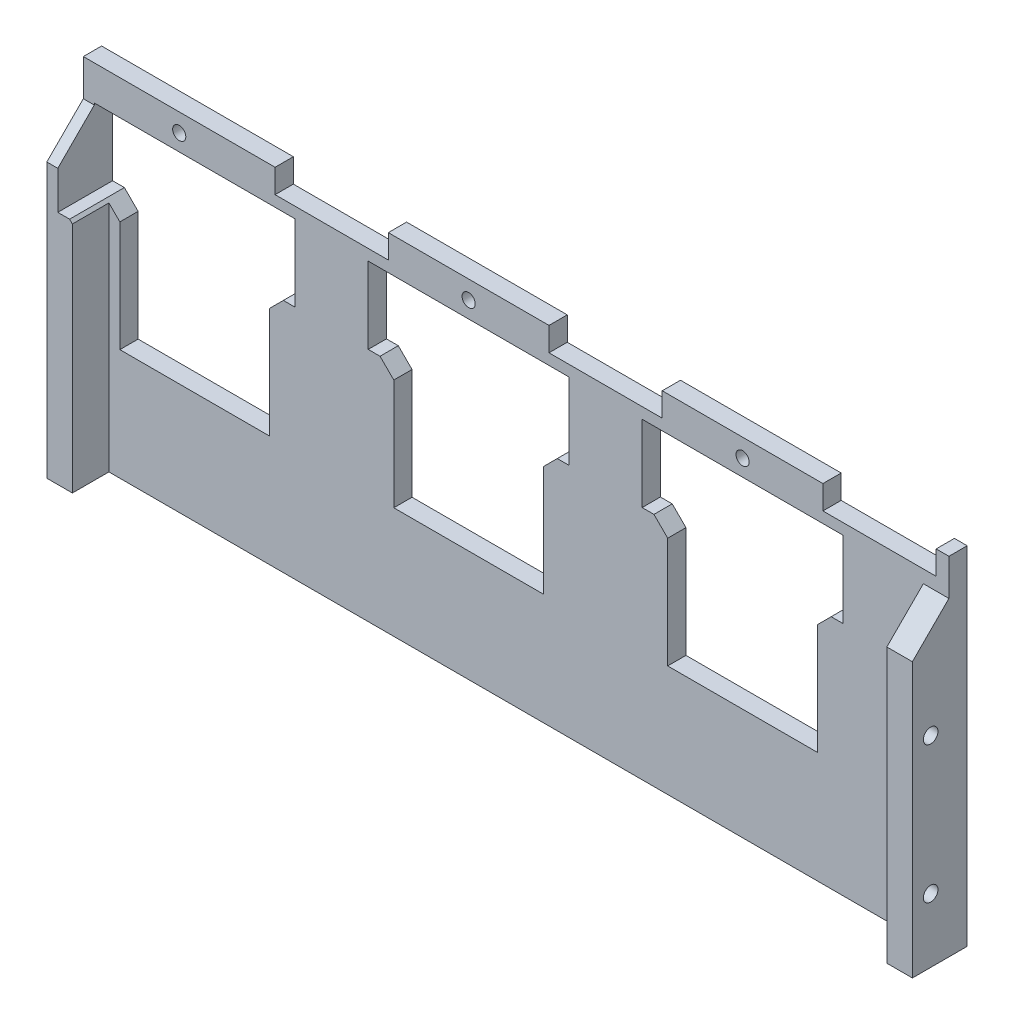
SolidWorks part; units mm, degrees
ref_plane "Płaszczyzna przednia" through (0, 0, 0) normal (0, 0, 1) x (1, 0, 0)
ref_plane "Płaszczyzna górna" through (0, 0, 0) normal (0, 1, 0) x (1, 0, 0)
ref_plane "Płaszczyzna prawa" through (0, 0, 0) normal (1, 0, 0) x (0, 0, -1)
sketch "Szkic1" plane through (0, 0, 0) normal (0, 0, 1) x (1, 0, 0)
  line L1 (-118.5, -72.5) -> (118.5, -72.5)
  line L2 (-118.5, -72.5) -> (-118.5, 72.5)
  line L3 (-118.5, 72.5) -> (118.5, 72.5)
  line L4 (118.5, -72.5) -> (118.5, 72.5)
  line L5 (0, 72.5) -> (0, -72.5) construction
  line L6 (-118.5, 0) -> (118.5, 0) construction
  point P0 (0, 0)
  dimension "D1" = 237
  dimension "D2" = 145
extrude "Dodanie-wyciągnięcie1" add sketch "Szkic1" along normal blind 5
sketch "Szkic2" plane through (0, 0, 5) normal (0, 0, 1) x (1, 0, 0)
  line L0 (118.5, -72.5) -> (118.5, 72.5) construction
  line L1 (118.5, 62.5) -> (111.5, 62.5)
  line L2 (118.5, 62.5) -> (118.5, -72.5)
  line L3 (118.5, -72.5) -> (111.5, -72.5)
  line L4 (111.5, 62.5) -> (111.5, -72.5)
  line L5 (115, -72.5) -> (115, 62.5) construction
  line L6 (118.5, -5) -> (111.5, -5) construction
  line L7 (118.5, 72.5) -> (-118.5, 72.5) construction
  line L9 (0, 0) -> (0, 72.5) construction
  line L10 (-118.5, -5) -> (-111.5, -5) construction
  line L11 (-115, -72.5) -> (-115, 62.5) construction
  line L12 (-111.5, 62.5) -> (-111.5, -72.5)
  line L13 (-118.5, -72.5) -> (-111.5, -72.5)
  line L14 (-118.5, 62.5) -> (-118.5, -72.5)
  line L15 (-118.5, 62.5) -> (-111.5, 62.5)
  line L16 (-118.5, -72.5) -> (118.5, -72.5) construction
  point P20 (-115, -5)
  point P300 (115, -5)
  dimension "D1" = 10
  dimension "D3" = 7
extrude "Dodanie-wyciągnięcie2" add sketch "Szkic2" along normal blind 10
sketch "Szkic3" plane through (118.5, 0, 0) normal (1, 0, 0) x (0, 0, -1)
  line L0 (-10, 62.5) -> (-10, -72.5) construction
  line L1 (-15, 62.5) -> (-5, 62.5) construction
  line L3 (0, -5) -> (-15, -5) construction
  line L5 (-15, -72.5) -> (-15, 62.5) construction
  line L6 (-15, -72.5) -> (-15, 62.5) construction
  line L7 (0, -72.5) -> (0, 72.5) construction
  line L8 (-15, -72.5) -> (0, -72.5) construction
  point P6 (-10, 32.5)
  point P7 (-10, -5)
  point P8 (-10, -42.5)
  dimension "D1" = 37.5
hole_wizard "Otwór Ø4.0 (4)1" positions "Szkic3" profile "Szkic4" hole size "Ø4.0" standard "DIN"
sketch "Szkic4" plane through (118.5, -42.5, 10) normal (0, 1, 0) x (0, 0, -1)
  line L0 (0, 0) -> (0, 6.7)
  line L1 (0, 6.7) -> (2, 6.7)
  line L2 (2, 6.7) -> (2, 0)
  line L5 (2, 0) -> (0, 0)
  line L10 (0, 6.7) -> (-2, 6.7) construction
  line L11 (0, -6.35) -> (0, 107.95) construction
  dimension "Średnica otworu" = 4
  dimension "Głębokość otworu" = 6.7
  dimension "Kąt wiertła" = 180
ref_plane "Płaszczyzna1" through (0, 0, 0) normal (-1, 0, 0) x (0, 0, 1)
mirror "Lustro1" about plane through (0, 0, 0) normal (-1, 0, 0) of "Otwór Ø4.0 (4)1"
chamfer "Sfazowanie1" distance 10 angle 45 2 edges at (-115, 62.5, 15) (115, 62.5, 15)
sketch "Szkic5" plane through (0, 0, 0) normal (0, 0, -1) x (-1, 0, 0)
  line L1 (-86, 42.5546) -> (-86, 42.5)
  line L2 (-84.5, 72.5) -> (-114.5, 72.5)
  line L4 (-11, 42.5546) -> (-11, 42.5)
  line L6 (-9.5, 72.5) -> (-39.5, 72.5)
  line L7 (64, 42.5546) -> (64, 42.5)
  line L12 (-86.2617, 42.0546) -> (-86.2617, 42.0546)
  line L15 (-86.2617, 42.0546) -> (-85.3536, 41.1464)
  line L16 (-85.3536, 41.1464) -> (-82.5, 38.2929)
  line L17 (-82.5, 38.2929) -> (-82.5, 8)
  line L22 (-82.5, 8) -> (-41.5, 8)
  line L39 (-41.5, 8) -> (-41.5, 38.2929)
  line L43 (111, 41.5) -> (112, 42.5) construction
  line L44 (-41.5, 38.2929) -> (-38.6464, 41.1464)
  line L46 (112, 42.5) -> (112, 48.5) construction
  line L48 (-38.6464, 41.1464) -> (-37.7383, 42.0546)
  line L49 (108, 38.5) -> (111, 41.5) construction
  line L57 (-37.7383, 42.0546) -> (-37.7383, 42.0546)
  line L58 (61, 62.5) -> (61, 42.5546) construction
  line L59 (61, 42.5546) -> (67.7879, 42.5546) construction
  line L86 (-37.7383, 42.0546) -> (-34.5, 42.0546)
  line L88 (-34.5, 42.0546) -> (-34.5, 63)
  line L90 (-34.5, 63) -> (-89.5, 63)
  line L94 (-89.5, 63) -> (-89.5, 42.0546)
  line L102 (-89.5, 42.0546) -> (-86.2617, 42.0546)
  line L103 (-84, 73) -> (-115, 73)
  line L104 (108.2121, 42.5546) -> (115, 42.5546) construction
  line L105 (115, 42.5546) -> (115, 62.5) construction
  line L106 (115, 62.5) -> (61, 62.5) construction
  line L109 (64, 42.5) -> (65, 41.5) construction
  line L110 (-115, 73) -> (-115, 66)
  line L115 (-115, 66) -> (-84, 66)
  line L121 (-84, 66) -> (-84, 73)
  line L122 (65, 41.5) -> (68, 38.5) construction
  line L123 (-11.2617, 42.0546) -> (-11.2617, 42.0546)
  line L127 (-11.2617, 42.0546) -> (-10.3536, 41.1464)
  line L128 (-10.3536, 41.1464) -> (-7.5, 38.2929)
  line L129 (-7.5, 38.2929) -> (-7.5, 8)
  line L132 (-7.5, 8) -> (33.5, 8)
  line L134 (33.5, 8) -> (33.5, 38.2929)
  line L135 (33.5, 38.2929) -> (36.3536, 41.1464)
  line L168 (36.3536, 41.1464) -> (37.2617, 42.0546)
  line L175 (37.2617, 42.0546) -> (37.2617, 42.0546)
  line L183 (37.2617, 42.0546) -> (40.5, 42.0546)
  line L200 (40.5, 42.0546) -> (40.5, 63)
  line L201 (40.5, 63) -> (-14.5, 63)
  line L206 (-14.5, 63) -> (-14.5, 42.0546)
  line L207 (-14.5, 42.0546) -> (-11.2617, 42.0546)
  line L208 (-9, 73) -> (-40, 73)
  line L209 (-40, 73) -> (-40, 66)
  line L210 (-40, 66) -> (-9, 66)
  line L212 (68, 38.5) -> (68, 8.5) construction
  line L213 (68, 8.5) -> (108, 8.5) construction
  line L214 (108, 8.5) -> (108, 38.5) construction
  line L215 (-9, 66) -> (-9, 73)
  line L216 (36, 41.5) -> (37, 42.5) construction
  line L225 (37, 42.5) -> (37, 48.5) construction
  line L230 (63.7383, 42.0546) -> (63.7383, 42.0546)
  line L277 (33, 38.5) -> (36, 41.5) construction
  line L278 (63.7383, 42.0546) -> (64.6464, 41.1464)
  line L279 (-14, 62.5) -> (-14, 42.5546) construction
  line L280 (-14, 42.5546) -> (-7.2121, 42.5546) construction
  line L288 (64.6464, 41.1464) -> (67.5, 38.2929)
  line L289 (67.5, 38.2929) -> (67.5, 8)
  line L290 (67.5, 8) -> (108.5, 8)
  line L292 (108.5, 8) -> (108.5, 38.2929)
  line L293 (108.5, 38.2929) -> (111.3536, 41.1464)
  line L294 (111.3536, 41.1464) -> (112.2617, 42.0546)
  line L296 (33.2121, 42.5546) -> (40, 42.5546) construction
  line L309 (40, 42.5546) -> (40, 62.5) construction
  line L310 (40, 62.5) -> (-14, 62.5) construction
  line L311 (-11, 42.5) -> (-10, 41.5) construction
  line L312 (112.2617, 42.0546) -> (112.2617, 42.0546)
  line L314 (112.2617, 42.0546) -> (115.5, 42.0546)
  line L318 (115.5, 42.0546) -> (115.5, 63)
  line L320 (-10, 41.5) -> (-7, 38.5) construction
  line L333 (115.5, 63) -> (60.5, 63)
  line L334 (60.5, 63) -> (60.5, 42.0546)
  line L335 (60.5, 42.0546) -> (63.7383, 42.0546)
  line L336 (35, 73) -> (35, 66)
  line L337 (35, 66) -> (66, 66)
  line L338 (66, 66) -> (66, 73)
  line L340 (66, 73) -> (35, 73)
  line L349 (-7, 38.5) -> (-7, 8.5) construction
  line L350 (-7, 8.5) -> (33, 8.5) construction
  line L351 (33, 8.5) -> (33, 38.5) construction
  line L352 (-42, 38.5) -> (-39, 41.5) construction
  line L355 (-39, 41.5) -> (-38, 42.5) construction
  line L356 (-38, 42.5) -> (-38, 48.5) construction
  line L358 (-86, 42.5) -> (-85, 41.5) construction
  line L362 (-85, 41.5) -> (-82, 38.5) construction
  line L364 (-89, 62.5) -> (-89, 42.5546) construction
  line L365 (-89, 42.5546) -> (-82.2121, 42.5546) construction
  line L373 (-41.7879, 42.5546) -> (-35, 42.5546) construction
  line L374 (-35, 42.5546) -> (-35, 62.5) construction
  line L375 (-35, 62.5) -> (-89, 62.5) construction
  line L391 (-82, 38.5) -> (-82, 8.5) construction
  line L392 (-82, 8.5) -> (-42, 8.5) construction
  line L393 (-42, 8.5) -> (-42, 38.5) construction
  line L395 (35.5, 90.5) -> (35.5, 66.5) construction
  line L396 (35.5, 66.5) -> (65.5, 66.5) construction
  line L397 (65.5, 66.5) -> (65.5, 90.5) construction
  line L399 (-39.5, 90.5) -> (-39.5, 66.5) construction
  line L400 (-39.5, 66.5) -> (-9.5, 66.5) construction
  line L401 (-9.5, 66.5) -> (-9.5, 90.5) construction
  line L402 (-114.5, 90.5) -> (-114.5, 66.5) construction
  line L403 (-114.5, 66.5) -> (-84.5, 66.5) construction
  line L404 (-84.5, 66.5) -> (-84.5, 90.5) construction
  line L407 (111, 41.5) -> (112, 42.5)
  line L408 (112, 42.5) -> (112, 42.5546)
  line L410 (108, 38.5) -> (111, 41.5)
  line L412 (61, 62.5) -> (61, 42.5546)
  line L413 (61, 42.5546) -> (64, 42.5546)
  line L421 (112, 42.5546) -> (115, 42.5546)
  line L422 (115, 42.5546) -> (115, 62.5)
  line L423 (115, 62.5) -> (61, 62.5)
  line L424 (64, 42.5) -> (65, 41.5)
  line L428 (65, 41.5) -> (68, 38.5)
  line L445 (68, 38.5) -> (68, 8.5)
  line L446 (68, 8.5) -> (108, 8.5)
  line L447 (108, 8.5) -> (108, 38.5)
  line L449 (36, 41.5) -> (37, 42.5)
  line L450 (37, 42.5) -> (37, 42.5546)
  line L452 (33, 38.5) -> (36, 41.5)
  line L454 (-14, 62.5) -> (-14, 42.5546)
  line L455 (-14, 42.5546) -> (-11, 42.5546)
  line L463 (37, 42.5546) -> (40, 42.5546)
  line L464 (40, 42.5546) -> (40, 62.5)
  line L465 (40, 62.5) -> (-14, 62.5)
  line L466 (-11, 42.5) -> (-10, 41.5)
  line L470 (-10, 41.5) -> (-7, 38.5)
  line L487 (-7, 38.5) -> (-7, 8.5)
  line L488 (-7, 8.5) -> (33, 8.5)
  line L489 (33, 8.5) -> (33, 38.5)
  line L490 (-42, 38.5) -> (-39, 41.5)
  line L493 (-39, 41.5) -> (-38, 42.5)
  line L494 (-38, 42.5) -> (-38, 42.5546)
  line L496 (-86, 42.5) -> (-85, 41.5)
  line L500 (-85, 41.5) -> (-82, 38.5)
  line L502 (-89, 62.5) -> (-89, 42.5546)
  line L503 (-89, 42.5546) -> (-86, 42.5546)
  line L511 (-38, 42.5546) -> (-35, 42.5546)
  line L512 (-35, 42.5546) -> (-35, 62.5)
  line L513 (-35, 62.5) -> (-89, 62.5)
  line L529 (-82, 38.5) -> (-82, 8.5)
  line L530 (-82, 8.5) -> (-42, 8.5)
  line L531 (-42, 8.5) -> (-42, 38.5)
  line L533 (35.5, 72.5) -> (35.5, 66.5)
  line L534 (35.5, 66.5) -> (65.5, 66.5)
  line L535 (65.5, 66.5) -> (65.5, 72.5)
  line L537 (-39.5, 72.5) -> (-39.5, 66.5)
  line L538 (-39.5, 66.5) -> (-9.5, 66.5)
  line L539 (-9.5, 66.5) -> (-9.5, 72.5)
  line L540 (-114.5, 72.5) -> (-114.5, 66.5)
  line L541 (-114.5, 66.5) -> (-84.5, 66.5)
  line L542 (-84.5, 66.5) -> (-84.5, 72.5)
  line L548 (-118.5, 72.5) -> (-118.5, -72.5)
  line L549 (-118.5, -72.5) -> (118.5, -72.5)
  line L550 (118.5, -72.5) -> (118.5, 72.5)
  line L551 (118.5, 72.5) -> (-118.5, 72.5)
  line L555 (65.5, 72.5) -> (35.5, 72.5)
  line M8 (118.5, 72.5) -> (-118.5, 72.5)
  dimension "D1" = 0
  dimension "D2" = 0.5
extrude "Wytnij-wyciągnięcie1" cut sketch "Szkic5" against normal up to next contours L530 L531 L490 L493 L494 L511 L512 L513 L502 L503 L1 L496 L500 L529 | L541 L542 L540 M8 | L542 L541 L540 L110 L115 L121 M8 | L94 L102 L15 L16 L17 L22 L39 L44 L48 L86 L88 L90 L531 L530 L529 L500 L496 L1 L503 L502 L513 L512 L511 L494 L493 L490 | L488 L489 L452 L449 L450 L463 L464 L465 L454 L455 L4 L466 L470 L487 | L206 L207 L127 L128 L129 L132 L134 L135 L168 L183 L200 L201 L489 L488 L487 L470 L466 L4 L455 L454 L465 L464 L463 L450 L449 L452 | L538 L539 L537 M8 | L539 L538 L537 L209 L210 L215 M8 | L446 L447 L410 L407 L408 L421 L422 L423 L412 L413 L7 L424 L428 L445 | L334 L335 L278 L288 L289 L290 L292 L293 L294 L314 L318 L333 L447 L446 L445 L428 L424 L7 L413 L412 L423 L422 L421 L408 L407 L410 | L534 L535 L533 M8 | L535 L534 L533 L336 L337 L338 M8 region at (62, 37.4744, 0) region at (99.5, 69.5, 0) region at (84.25, 72.1833, 0) region at (39.75, 72.1833, 0) region at (24.5, 69.5, 0) region at (-35.25, 72.1833, 0) region at (-50.5, 69.5, 0) region at (-13, 37.4744, 0) region at (-88, 37.4744, 0) region at (87.8809, 42.1324, 0) region at (12.8809, 42.1324, 0) region at (-62.1191, 42.1324, 0)
ref_plane "Płaszczyzna2" through (0, -22.5, 0) normal (0, -1, 0) x (-1, 0, 0)
split "Podziel1" trim tools "Płaszczyzna2" bodies to split 113 resulting bodies 107 108
sketch "Szkic6" plane through (0, 0, 0) normal (0, 0, -1) x (-1, 0, 0)
  line L3 (-62, 72.5) -> (-62, 67.5) construction
  line L4 (-84, 72.5) -> (-40, 72.5) construction
  line L6 (13, 72.5) -> (13, 67.5) construction
  line L7 (-9, 72.5) -> (35, 72.5) construction
  line L9 (92.25, 72.5) -> (92.25, 67.5) construction
  line L10 (66, 72.5) -> (118.5, 72.5) construction
  point P18 (-62, 67.5)
  point P20 (13, 67.5)
  point P22 (92.25, 67.5)
  dimension "D1" = 5
hole_wizard "Pogłębienie walcowe pod M3 Śrubę z łbem stożkowym ściętym1" positions "Szkic6" profile "Szkic7" counterbore size "M3" standard "DIN"
sketch "Szkic7" plane through (62, 67.5, 0) normal (1, 0, 0) x (0, 1, 0)
  line L0 (0, 0) -> (0, 7.7815)
  line L1 (0, 7.7815) -> (1.8, 6.7)
  line L2 (1.8, 6.7) -> (1.8, 2.4)
  line L3 (1.8, 2.4) -> (3.5, 2.4)
  line L4 (3.5, 2.4) -> (3.5, 0)
  line L5 (3.5, 0) -> (0, 0)
  line L10 (0, 7.7815) -> (-1.8, 6.7) construction
  line L11 (0, -6.35) -> (0, 107.95) construction
  dimension "Średnica otworu" = 3.6
  dimension "Głębokość otworu" = 6.7
  dimension "Średnica pogłębienia walcowego" = 7
  dimension "Głębokość pogłębienia walcowego" = 2.4
  dimension "Kąt wiertła" = 118
delete or keep bodies "Obiekt-Usuń/zachowaj 1" type delete bodies bodies 108
